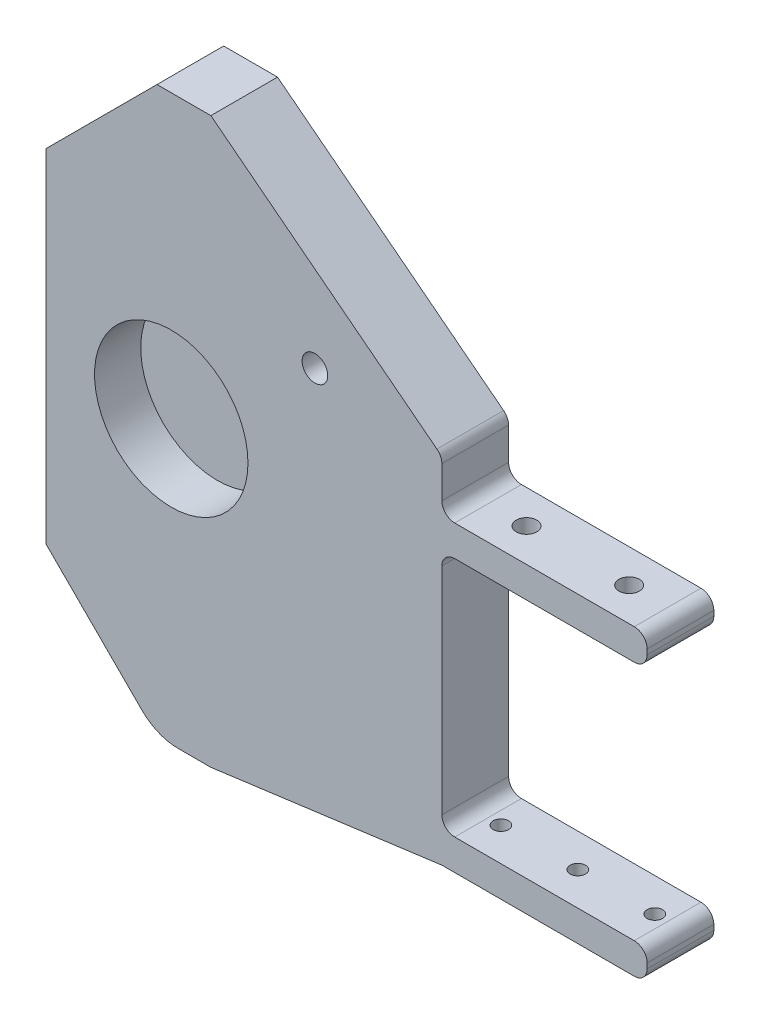
SolidWorks part; units mm, degrees
material "5052-H36"
ref_plane "Plano frontal" through (0, 0, 0) normal (0, 0, 1) x (1, 0, 0)
ref_plane "Plano superior" through (0, 0, 0) normal (0, 1, 0) x (1, 0, 0)
ref_plane "Plano direito" through (0, 0, 0) normal (1, 0, 0) x (0, 0, -1)
sketch "Esboço1" plane through (0, 0, 0) normal (0, 0, 1) x (1, 0, 0)
  line L0 (79.1281, 0) -> (0, 0) construction
  line L3 (4.9801, 55) -> (32.742, 55)
  line L6 (32.742, 55) -> (-22.7817, 55)
  line L12 (-22.7817, 55) -> (-44.3754, 33.4063)
  line L14 (-44.3754, -33.4063) -> (-22.7817, -55)
  line L15 (-22.7817, -55) -> (32.742, -55)
  line L18 (393.8557, 316.0739) -> (396.402, 318.6203) [skipped]
  line L19 (55, 501.996) -> (55, 520.8093) [skipped]
  line L20 (-316.0739, 393.8557) -> (-318.6203, 396.402) [skipped]
  line L21 (32.742, 55) -> (32.742, 10)
  line L22 (32.742, -49) -> (32.742, -55)
  line L23 (32.742, -49) -> (72.742, -49)
  line L25 (32.742, -43) -> (72.742, -43)
  line L26 (72.742, -49) -> (72.742, -43)
  line L27 (32.742, 4) -> (32.742, -43)
  line L28 (32.742, 4) -> (72.742, 4)
  line L30 (32.742, 10) -> (72.742, 10)
  line L31 (72.742, 4) -> (72.742, 10)
  line L32 (-44.3754, 33.4063) -> (-44.3754, -33.4063)
  line L34 (-55, 7.7563) -> (-55, -6.3461) [skipped]
  circle A0 centre (0, 0) radius 15 construction
  arc A3 (4.9801, 55) -> (0, -55.225) centre (0, 0) ccw construction
  point P14 (4.9801, 55)
  dimension "D1" = 30
  dimension "D5" = 110
  dimension "D6" = 40
  dimension "D7" = 6
  dimension "D8" = 6
  dimension "D9" = 45
extrude "Ressalto-extrusão1" add sketch "Esboço1" along normal mid plane 13 contours L14 L15 L3 L6 L12 A0 region at (-0.7875, -1.1016, 0)
sketch "Esboço2" plane through (0, 0, 6.5) normal (0, 0, 1) x (1, 0, 0)
  circle A1 centre (-20, 0) radius 14.95
  dimension "D1" = 29.9
  dimension "D2" = 20
extrude "Corte-extrusão1" cut sketch "Esboço2" against normal blind 9
sketch "Esboço3" plane through (0, 0, 6.5) normal (0, 0, 1) x (1, 0, 0)
  line L0 (-22.7817, -55) -> (32.742, -55) construction
  line L1 (-12.2817, -55) -> (32.742, -49)
  line L2 (32.742, -49) -> (32.742, -55)
  line L3 (32.742, -55) -> (-12.2817, -55)
  line L4 (-12.2817, -55) -> (-12.2817, 66.3095) construction
  line L6 (32.742, 10) -> (72.742, 10) construction
  line L11 (32.742, 55) -> (-12.2817, 55)
  line L12 (-12.2817, 55) -> (32.742, 20)
  line L13 (32.742, 20) -> (32.742, 55)
  circle A0 centre (8, 22.5) radius 2.5
  point P0 (-12.2817, -55)
  dimension "D2" = 5
  dimension "D1" = 10.5
  dimension "D3" = 22.5
  dimension "D4" = 28
  dimension "D5" = 10
extrude "Corte-extrusão2" cut sketch "Esboço3" against normal blind 13
fillet "Filete1" radius 10 1 edges at (-22.7817, -55, 0)
sketch "Esboço4" plane through (0, 0, -6.5) normal (0, 0, -1) x (-1, 0, 0)
  line L0 (44.3754, 33.4063) -> (44.3754, -33.4063) construction
  circle A0 centre (36.3754, 8.4063) radius 2
  circle A1 centre (12.9554, -16.5937) radius 2
  circle A2 centre (22.3754, -27.5937) radius 2
  dimension "D1" = 4
  dimension "D2" = 25
  dimension "D3" = 8
  dimension "D4" = 23.42
  dimension "D5" = 25
  dimension "D6" = 36
  dimension "D7" = 14
extrude "Corte-extrusão3" cut sketch "Esboço4" against normal blind 10
sketch "Esboço6" plane through (0, 10, 0) normal (0, 1, 0) x (1, 0, 0)
  circle A0 centre (42.742, -0.0016) radius 2
  circle A1 centre (62.742, -0.0016) radius 2
  circle A2 centre (42.742, -0.0016) radius 2 construction
  point P9 (62.742, -0.0016)
  dimension "D1" = 20
extrude "Corte-extrusão4" cut sketch "Esboço6" against normal blind 10
sketch "Esboço7" plane through (0, -49, 0) normal (0, -1, 0) x (1, 0, 0)
  line L0 (32.742, -6.5) -> (72.742, -6.5) construction
  line L1 (37.742, 0) -> (67.742, 0) construction
  line L2 (72.742, 6.5) -> (72.742, -6.5) construction
  circle A0 centre (37.742, 0) radius 1.5
  circle A1 centre (52.742, 0) radius 1.5
  circle A2 centre (67.742, 0) radius 1.5
  dimension "D1" = 3
  dimension "D2" = 6.5
  dimension "D3" = 5
  dimension "D4" = 20
  dimension "D5" = 35
extrude "Corte-extrusão5" cut sketch "Esboço7" against normal blind 10
fillet "Filete2" radius 2.5 8 edges at (72.742, -49, 0) (72.742, -43, 0) (72.742, 4, 0) (72.742, 10, 0) (32.742, 20, 0) (32.742, -43, 0) (32.742, 10, 0) (32.742, 4, 0)
